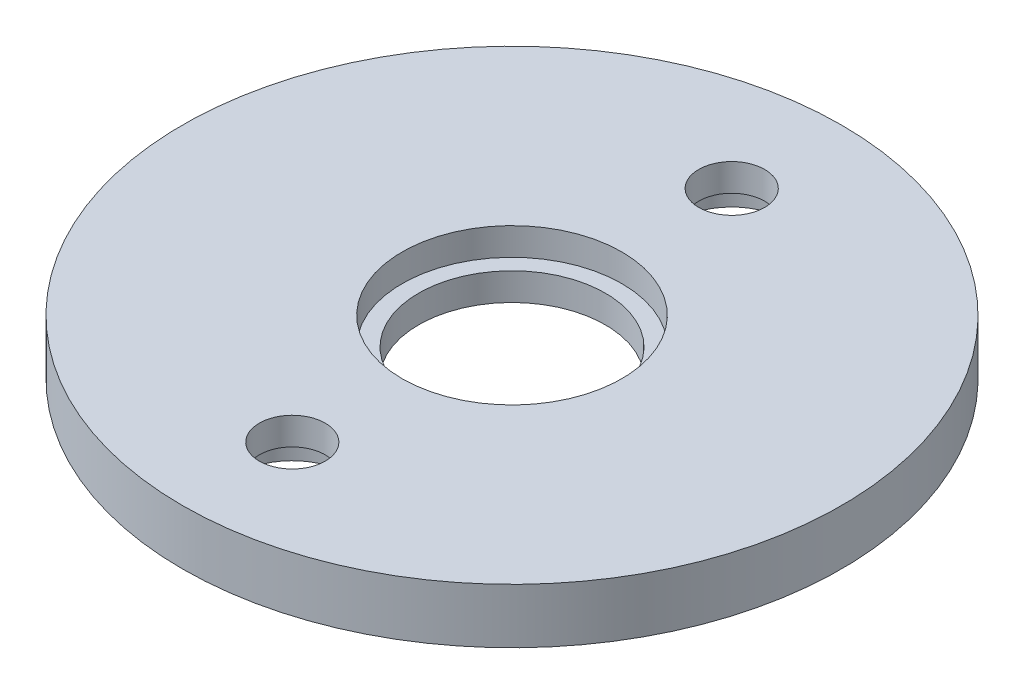
SolidWorks part; units mm, degrees
ref_plane "Front Plane" through (0, 0, 0) normal (0, 0, 1) x (1, 0, 0)
ref_plane "Top Plane" through (0, 0, 0) normal (0, 1, 0) x (1, 0, 0)
ref_plane "Right Plane" through (0, 0, 0) normal (1, 0, 0) x (0, 0, -1)
sketch "Sketch1" plane through (0, 0, 0) normal (0, 1, 0) x (1, 0, 0)
  line L0 (0, 0) -> (0, 4) construction
  line L1 (0, 0) -> (-2.2751, 0) construction
  circle A0 centre (0, 0) radius 6
  circle A1 centre (0, 4) radius 0.6
  circle A2 centre (0, 4) radius 1
  circle A3 centre (0, -4) radius 1
  circle A4 centre (0, -4) radius 0.6
  circle A5 centre (0, 0) radius 1.7
  dimension "D1" = 12
  dimension "D3" = 1.2
  dimension "D4" = 2
  dimension "D5" = 3.4
  dimension "D2" = 4
extrude "BasePlate" add sketch "Sketch1" along normal blind 1 contours A0 A5 A2 A3 | A4 | A1 | A2 A1 | A3 A4 region at (-5.8303, 0, 0) region at (0, 0, -4) region at (-0.9717, 0, -4) region at (-0.9717, 0, 4) region at (0, 0, 4)
extrude "ScrewHoles" cut sketch "Sketch1<3>" along normal through all contours A4 | A1 region at (0, 0, -4) region at (0, 0, 4)
sketch "Sketch1<3>" plane through (0, 0, 0) normal (0, 1, 0) x (1, 0, 0) same geometry as "Sketch1"
extrude "ScrewHatSlots" cut sketch "Sketch1<4>" along normal blind 0.5 contours A3 A4 | A2 A1 region at (-0.9717, 0, -4) region at (-0.9717, 0, 4)
sketch "Sketch1<4>" plane through (0, 0, 0) normal (0, 1, 0) x (1, 0, 0) same geometry as "Sketch1"
sketch "Sketch2" plane through (0, 1, 0) normal (0, 1, 0) x (1, 0, 0)
  circle A0 centre (0, 0) radius 2
  dimension "D1" = 4
extrude "BearingSlot" cut sketch "Sketch2" against normal offset from surface (0.5 mm away) 0.5 up to face at (0, 0, 1.7)
equation "\"BoltD\"=2mm"
equation "\"BoltHatD\"=3.2mm"
equation "\"SmallScrewD\"=1.2mm"
equation "\"SmallScrewHatD\"=2mm"
equation "\"TubeOuterD\"=1.2mm"
equation "\"BasicPulleyD\"=15mm"
equation "\"GrooveDepth\"=0.7mm"
equation "\"Cable1D\"=0.4mm"
equation "\"Cable2D\"=0.3mm"
equation "\"BallBearingInnerD\"=2mm"
equation "\"BallBearingOuterD\"=4mm"
equation "\"BallBearingThickness\"=2mm"
equation "\"BearingCapD\"=12mm"
equation "\"HumerusL\"=37.2mm"
equation "\"HumerusElbowSidePulleyD\"=10mm"
equation "\"RadiusL\"=68.1mm"
equation "\"Finger1L\"=120mm"
equation "\"Finger2L\"=100mm"
equation "\"Finger3L\"=80mm"
equation "\"ElbowExtendedAngle\"=140deg"
equation "\"D1@Sketch1\"=\"BearingCapD\""
equation "\"D3@Sketch1\"=\"SmallScrewD\""
equation "\"D4@Sketch1\"=\"SmallScrewHatD\""
equation "\"D5@Sketch1\"=\"BallBearingOuterD\"-0.6"
equation "\"D1@Sketch2\"=\"BallBearingOuterD\""
equation "\"TubeClipW\"=1.5mm"
equation "\"TubeClipH\"=1.5mm"
equation "\"TubeClipLock_SideL\"=1.5mm"
equation "\"TubeClipLock_W\"=0.7mm"
equation "\"ElbowFlexedAngle\"=38deg"
equation "\"Digit5ExtendedAngle\"=80deg"
equation "\"Digit5FlexedAngle\"=24deg"
equation "\"Digit4ExtendedAngle\"=108deg"
equation "\"Digit4FlexedAngle\"=34deg"
equation "\"Digit3ExtendedAngle\"=145deg"
equation "\"Digit3FlexedAngle\"=44deg"
equation "\"NutD\"=3.9mm"
equation "\"XL330_M077_T_FrameBoltD\"=1.6mm"
equation "\"XL330_M077_T_FrameBoltHatD\"=2.9mm"
equation "\"XL330_M077_T_FrameNutD\"=2.5mm"
equation "\"KST_ServoShaftBoltD\"=2.5mm"
equation "\"KST_ServoShaftBoltHatD\"=5.2mm"
equation "\"XL330_M077_T_HornScrewD\"=1.9mm"
equation "\"XL330_M077_T_HornScrewHatD\"=3.3mm"
